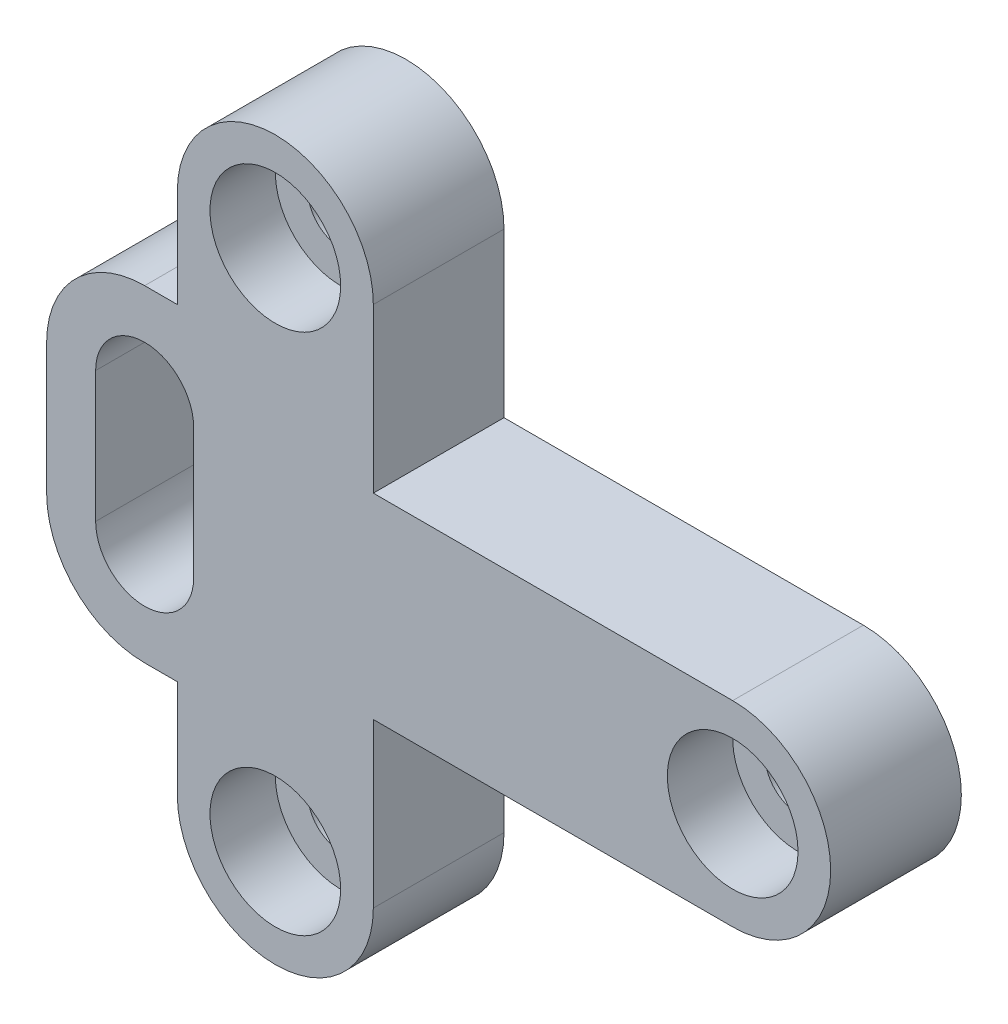
SolidWorks part; units mm, degrees
ref_plane "Ön Düzlem" through (0, 0, 0) normal (0, 0, 1) x (1, 0, 0)
ref_plane "Üst Düzlem" through (0, 0, 0) normal (0, 1, 0) x (1, 0, 0)
ref_plane "Sağ Düzlem" through (0, 0, 0) normal (1, 0, 0) x (0, 0, -1)
sketch "Çizim1" plane through (0, 0, 0) normal (0, 0, 1) x (1, 0, 0)
  line L0 (-20, 10) -> (-20, -10) construction
  line L1 (15.0006, -15) -> (15.0006, -40)
  line L2 (-20, 10) -> (-20, -10) construction
  line L5 (15.0006, 40) -> (15.0006, 15)
  line L6 (-14.9994, 40) -> (-14.9994, 25)
  line L7 (-12.5, 10) -> (-12.5, -10)
  line L8 (-27.5, 10) -> (-27.5, -10)
  line L10 (-14.9994, 28.6848) -> (-14.9994, 25)
  line L12 (-35, 10) -> (-35, -10)
  line L13 (-20, 25) -> (-14.9994, 25)
  line L14 (-20, -25) -> (-14.9994, -25)
  line L16 (-14.9994, -25) -> (-14.9994, -40)
  line L17 (15.0006, 0) -> (70.0006, 0) construction
  line L18 (15.0006, 15) -> (70.0006, 15)
  line L19 (15.0006, -15) -> (70.0006, -15)
  arc A0 (15.0006, 40) -> (-14.9994, 40) centre (0.0006, 40) ccw
  arc A1 (-14.9994, -40) -> (15.0006, -40) centre (0.0006, -40) ccw
  arc A2 (-12.5, 10) -> (-27.5, 10) centre (-20, 10) ccw
  arc A3 (-27.5, -10) -> (-12.5, -10) centre (-20, -10) ccw
  arc A5 (-35, -10) -> (-20, -25) centre (-20, -10) ccw
  arc A6 (-20, 25) -> (-35, 10) centre (-20, 10) ccw
  circle A7 centre (0.0006, -40) radius 10
  circle A8 centre (0.0006, -40) radius 5
  circle A9 centre (0.0006, 40) radius 10
  circle A10 centre (0.0006, 40) radius 5
  arc A12 (70.0006, -15) -> (70.0006, 15) centre (70.0006, 0) ccw
  circle A13 centre (70.0006, 0) radius 10
  circle A14 centre (70.0006, 0) radius 5
  point P3 (84.1246, 0.0262)
  point P4 (70, 0.0262)
  point P7 (0, 0)
  point P8 (0, 0)
  point P16 (-20, 0)
  point P23 (-20, 0)
  point P33 (42.5006, -1.2772)
  point P40 (21.3485, 28.5828)
  point P43 (71.2358, -1.2772)
  dimension "D3" = 15
  dimension "D6" = 7.5
  dimension "D9" = 15
  dimension "D10" = 10
  dimension "D11" = 20
  dimension "D2" = 15
  dimension "D4" = 70
  dimension "D5" = 20.0006
  dimension "D7" = 80
  dimension "D8" = 20
  dimension "D12" = 40
  dimension "D13" = 40
  dimension "D14" = 30
  dimension "D15" = 30
extrude "Yükseklik-Ekstrüzyon1" add sketch "Çizim1" along normal blind 20 contours L19 A12 L18 L5 A0 L6 L13 A6 L12 A5 L14 L16 A1 L1 A3 L8 A2 L7 A7 A9 A13 region at (13.6502, 0, 0)
extrude "Yükseklik-Ekstrüzyon2" add sketch "Çizim1<3>" along normal blind 10 contours A9 A10 | A7 A8 | A13 A14 region at (-9.7165, -40, 0) region at (-9.7165, 40, 0) region at (60.2835, 0, 0)
sketch "Çizim1<3>" plane through (0, 0, 0) normal (0, 0, 1) x (1, 0, 0) same geometry as "Çizim1"
